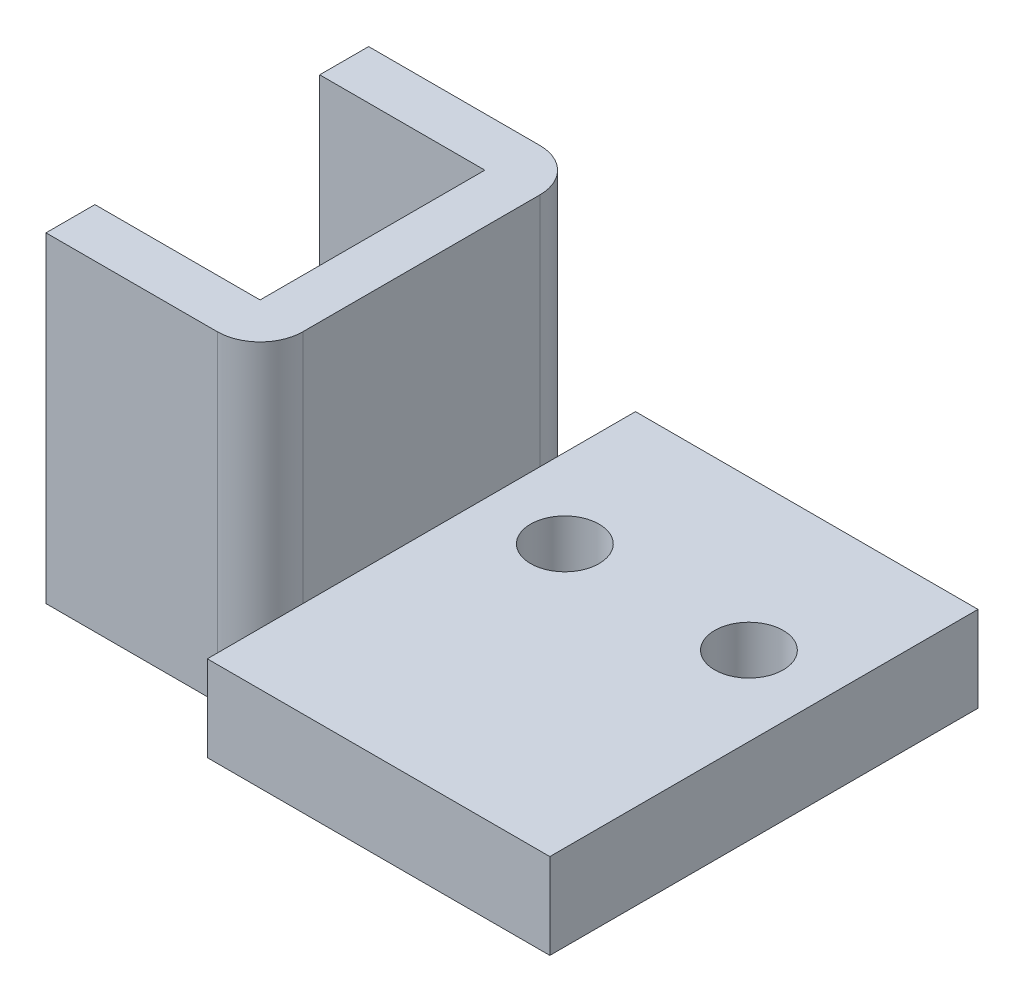
SolidWorks part; units mm, degrees
ref_plane "前视基准面" through (0, 0, 0) normal (0, 0, 1) x (1, 0, 0)
ref_plane "上视基准面" through (0, 0, 0) normal (0, 1, 0) x (1, 0, 0)
ref_plane "右视基准面" through (0, 0, 0) normal (1, 0, 0) x (0, 0, -1)
sketch "草图3" plane through (0, 0, 0) normal (0, 1, 0) x (1, 0, 0)
  line L0 (-6.3835, 11.8607) -> (-6.3835, -3.2093)
  line L1 (-6.3835, -3.2093) -> (1.6165, -3.2093)
  line L2 (3.6165, -1.2093) -> (3.6165, 9.8607)
  line L3 (1.6165, 11.8607) -> (-6.3835, 11.8607)
  line L4 (3.6165, 14.3257) -> (3.6165, -5.6743)
  line L5 (3.6165, -5.6743) -> (19.6165, -5.6743)
  line L6 (19.6165, -5.6743) -> (19.6165, 14.3257)
  line L7 (19.6165, 14.3257) -> (3.6165, 14.3257)
  line L8 (-6.3835, 9.5757) -> (1.3315, 9.5757)
  line L9 (1.3315, 9.5757) -> (1.3315, -0.9243)
  line L10 (1.3315, -0.9243) -> (-6.3835, -0.9243)
  line L11 (-6.3835, -0.9243) -> (-6.3835, 9.5757)
  arc A0 (1.6165, -3.2093) -> (3.6165, -1.2093) centre (1.6165, -1.2093) ccw
  arc A1 (3.6165, 9.8607) -> (1.6165, 11.8607) centre (1.6165, 9.8607) ccw
  dimension "D1" = 2
  dimension "D2" = 16
  dimension "D3" = 20
  dimension "D4" = 2.465
  dimension "D5" = 15.07
  dimension "D6" = 8
  dimension "D7" = 2.285
  dimension "D8" = 2.285
  dimension "D9" = 2.285
extrude "凸台-拉伸3" add sketch "草图3" along normal blind 15 contours L2 A1 L3 L0 L1 A0 region at (-2.3835, 0, -11.6798)
extrude "凸台-拉伸4" add sketch "草图3<4>" along normal blind 4 contours L6 L7 L4 L2 L5 region at (11.6165, 0, -4.3257)
sketch "草图3<4>" plane through (0, 0, 0) normal (0, 1, 0) x (1, 0, 0) same geometry as "草图3"
sketch "草图8" plane through (0, 4, 0) normal (0, 1, 0) x (1, 0, 0)
  line L0 (19.6165, 14.3257) -> (3.6165, 14.3257) construction
  line L2 (3.6165, 14.3257) -> (3.6165, 9.8607) construction
  circle A0 centre (7.3165, 7.3257) radius 1.6
  circle A1 centre (15.9165, 7.3257) radius 1.6
  dimension "D1" = 3.2
  dimension "D2" = 3.2
  dimension "D3" = 7
  dimension "D4" = 7
  dimension "D5" = 3.7
  dimension "D6" = 8.6
extrude "切除-拉伸1" cut sketch "草图8" against normal through all
